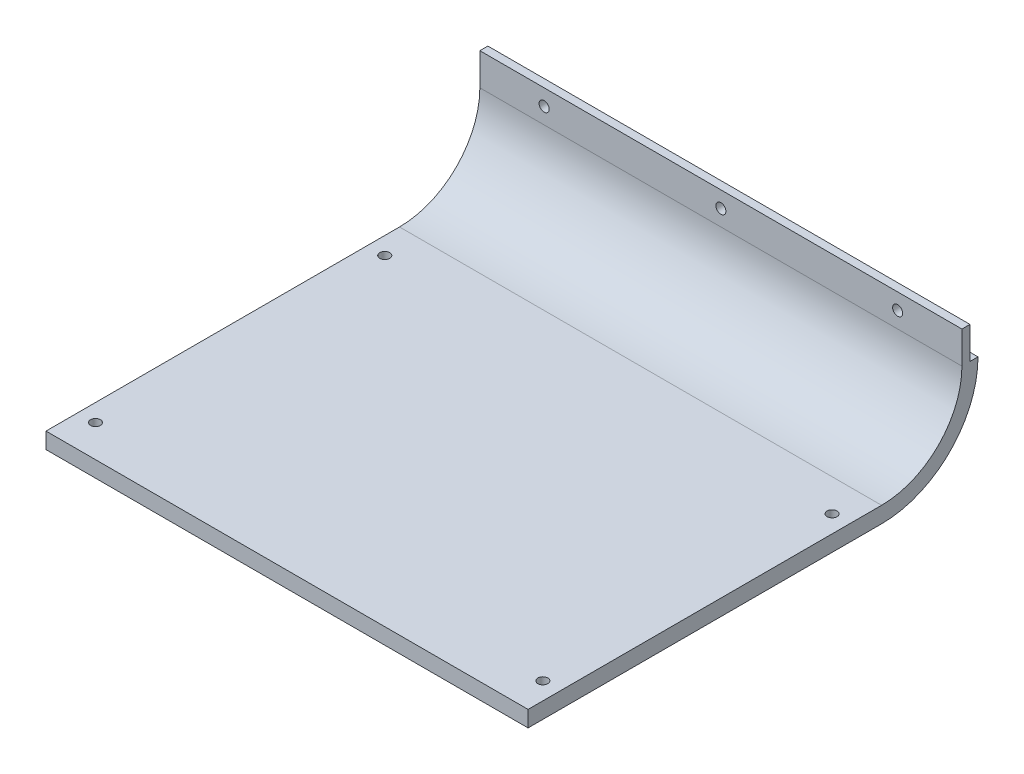
SolidWorks part; units mm, degrees
material "6061-T6 Aluminum"
ref_plane "Front Plane" through (0, 0, 0) normal (0, 0, 1) x (1, 0, 0)
ref_plane "Top Plane" through (0, 0, 0) normal (0, 1, 0) x (1, 0, 0)
ref_plane "Right Plane" through (0, 0, 0) normal (1, 0, 0) x (0, 0, -1)
sketch "Sketch1" plane through (0, 0, 0) normal (1, 0, 0) x (0, 0, -1)
  line L0 (-139.7, 0) -> (139.7, 0)
  line L5 (139.7, 0) -> (139.7, 12.7) construction
  line L7 (-139.7, 12.7) -> (139.7, 12.7)
  line L9 (-139.7, 0) -> (-139.7, 12.7)
  line L12 (139.7, 0) -> (139.7, 152.4) construction
  line L13 (0.6365, 139.0796) -> (-139.7417, 139.9778) construction
  line L14 (-12.6991, 151.8652) -> (-139.6605, 152.6775) construction
  line L15 (203.2, 76.2) -> (215.9, 76.2)
  arc A2 (139.7, 0) -> (-12.6991, 151.8652) centre (139.7, 152.4) ccw construction
  arc A3 (139.7, 12.7) -> (0.6365, 139.0796) centre (139.7, 152.4) ccw construction
  circle A5 centre (139.7, 76.2) radius 76.2 construction
  arc A6 (215.9, 76.2) -> (139.7, 0) centre (139.7, 76.2) cw
  circle A7 centre (139.7, 76.2) radius 63.5 construction
  arc A8 (203.2, 76.2) -> (139.7, 12.7) centre (139.7, 76.2) cw
  point P3 (0, 0)
  dimension "D1" = 152.4
  dimension "D2" = 12.7
  dimension "D4" = 127
  dimension "D6" = 12.7
  dimension "D3" = 12.7
  dimension "D5" = 12.7
  dimension "D7" = 355.6
extrude "Boss-Extrude1" add sketch "Sketch1" along normal blind 190.5 and the other way blind 190.5
sketch "Sketch2" plane through (0, 76.2, 0) normal (0, 1, 0) x (1, 0, 0)
  line L0 (-190.5, 215.9) -> (-190.5, 203.2) construction
  line L1 (-190.5, 209.55) -> (190.5, 209.55)
  line L2 (-190.5, 209.55) -> (-190.5, 203.2)
  line L3 (-190.5, 203.2) -> (190.5, 203.2)
  line L4 (190.5, 209.55) -> (190.5, 203.2)
extrude "Boss-Extrude2" add sketch "Sketch2" along normal blind 25.4
sketch "Sketch3" plane through (0, 0, -209.55) normal (0, 0, -1) x (-1, 0, 0)
  line L0 (-190.5, 88.9) -> (190.5, 88.9) construction
  line L1 (-190.5, 101.6) -> (-190.5, 76.2) construction
  line L2 (190.5, 101.6) -> (190.5, 76.2) construction
  line L3 (-139.7, 101.6) -> (-139.7, 76.2) construction
  line L4 (-190.5, 101.6) -> (190.5, 101.6) construction
  line L5 (-190.5, 76.2) -> (190.5, 76.2) construction
  line L6 (0, 101.6) -> (0, 76.2) construction
  line L7 (190.5, 76.2) -> (-190.5, 76.2) construction
  line L8 (139.7, 101.6) -> (139.7, 76.2) construction
  circle A0 centre (-139.7, 88.9) radius 3.9687
  circle A1 centre (139.7, 88.9) radius 3.9687
  circle A2 centre (0, 88.9) radius 3.9687
  dimension "D3" = 7.9375
  dimension "D1" = 139.7
  dimension "D2" = 139.7
extrude "Cut-Extrude1" cut sketch "Sketch3" against normal blind 25.4
sketch "Sketch4" plane through (0, 12.7, 0) normal (0, 1, 0) x (1, 0, 0)
  line L0 (0, -139.7) -> (0, -114.3) construction
  line L1 (-190.5, -139.7) -> (190.5, -139.7) construction
  line L2 (0, -114.3) -> (0, 0) construction
  line L3 (0, 0) -> (0, 114.3) construction
  line L4 (0, 114.3) -> (0, 139.7) construction
  line L5 (-190.5, 139.7) -> (190.5, 139.7) construction
  line L6 (-176.784, 114.3) -> (176.784, 114.3) construction
  line L7 (-176.784, 0) -> (176.784, 0) construction
  line L8 (-176.784, -114.3) -> (176.784, -114.3) construction
  line L10 (190.5, 139.7) -> (190.5, -139.7) construction
  circle A0 centre (176.784, -114.3) radius 3.937
  circle A2 centre (176.784, 114.3) radius 3.937
  circle A3 centre (-176.784, -114.3) radius 3.937
  circle A5 centre (-176.784, 114.3) radius 3.937
  point P12 (0, 114.3)
  point P15 (0, 0)
  point P19 (0, -114.3)
  dimension "D3" = 7.874
  dimension "D1" = 228.6
  dimension "D2" = 13.716
extrude "Cut-Extrude2" cut sketch "Sketch4" against normal through all
